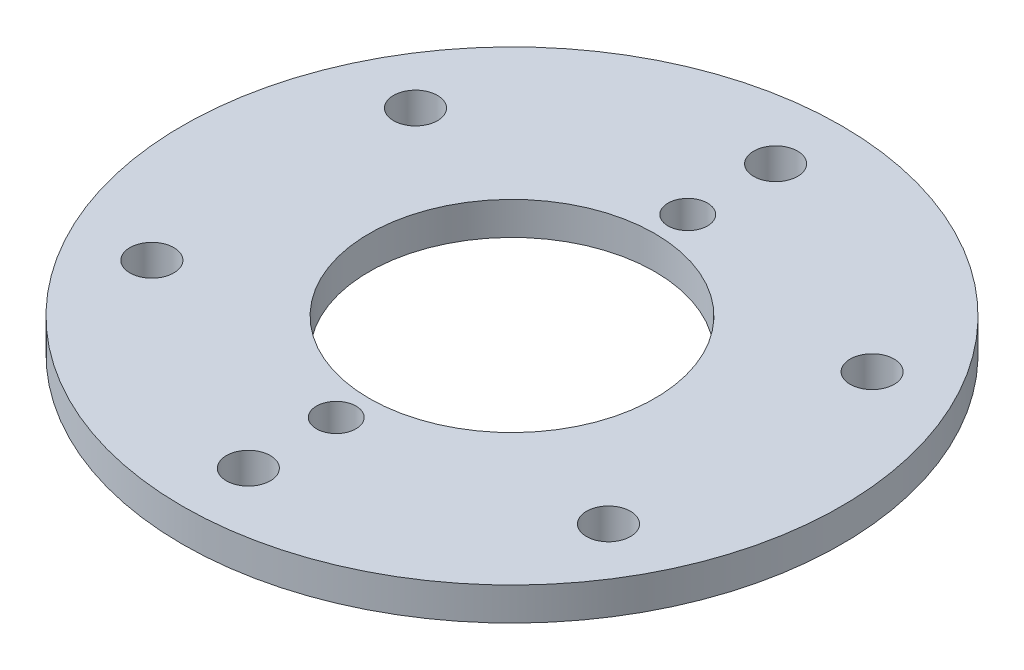
SolidWorks part; units mm, degrees
ref_plane "Front Plane" through (0, 0, 0) normal (0, 0, 1) x (1, 0, 0)
ref_plane "Top Plane" through (0, 0, 0) normal (0, 1, 0) x (1, 0, 0)
ref_plane "Right Plane" through (0, 0, 0) normal (1, 0, 0) x (0, 0, -1)
ref_axis "Axis1" through (0, -0.75, 0) along (0, 1, 0)
sketch "Sketch2" plane through (0, 0, 0) normal (0, 1, 0) x (1, 0, 0)
  circle A0 centre (0, 0) radius 150
  circle A1 centre (0, 0) radius 65
  dimension "D1" = 300
  dimension "D2" = 130
extrude "Boss-Extrude1" add sketch "Sketch2" along normal blind 15
sketch "Sketch3" plane through (0, 15, 0) normal (0, 1, 0) x (1, 0, 0)
  circle A0 centre (0, 0) radius 120
  point P3 (0, 120)
  dimension "D1" = 240
hole_wizard "Tap Drill for M14x2.0 Tap1" positions "Sketch3" profile "Sketch4" hole size "M14x2.0" standard "ANSI Metric" end condition through all
sketch "Sketch4" plane through (0, 15, -120) normal (1, 0, 0) x (0, 0, 1)
  line L0 (0, 0) -> (0, 15)
  line L1 (0, 15) -> (10, 15)
  line L2 (10, 15) -> (10, 0)
  line L5 (10, 0) -> (0, 0)
  line L11 (0, -6.35) -> (0, 107.95) construction
  dimension "Thru Hole Dia." = 20
  dimension "Thru Hole Depth" = 15
pattern_circular "CirPattern1" count 6 over 360 about axis through (0, -0.75, 0) along (0, 1, 0) of "Tap Drill for M14x2.0 Tap1"
sketch "Sketch5" plane through (0, 15, 0) normal (0, 1, 0) x (1, 0, 0)
  point P0 (0, 80)
  dimension "D1" = 80
hole_wizard "Tap Drill for M14x2.0 Tap2" positions "Sketch5" profile "Sketch6" hole size "M14x2.0" standard "ANSI Metric" end condition through all
sketch "Sketch6" plane through (0, 15, -80) normal (1, 0, 0) x (0, 0, 1)
  line L0 (0, 0) -> (0, 15)
  line L1 (0, 15) -> (9, 15)
  line L2 (9, 15) -> (9, 0)
  line L5 (9, 0) -> (0, 0)
  line L11 (0, -6.35) -> (0, 107.95) construction
  dimension "Thru Hole Dia." = 18
  dimension "Thru Hole Depth" = 15
pattern_circular "CirPattern2" count 2 over 360 about axis through (0, -0.75, 0) along (0, 1, 0) of "Tap Drill for M14x2.0 Tap2"
